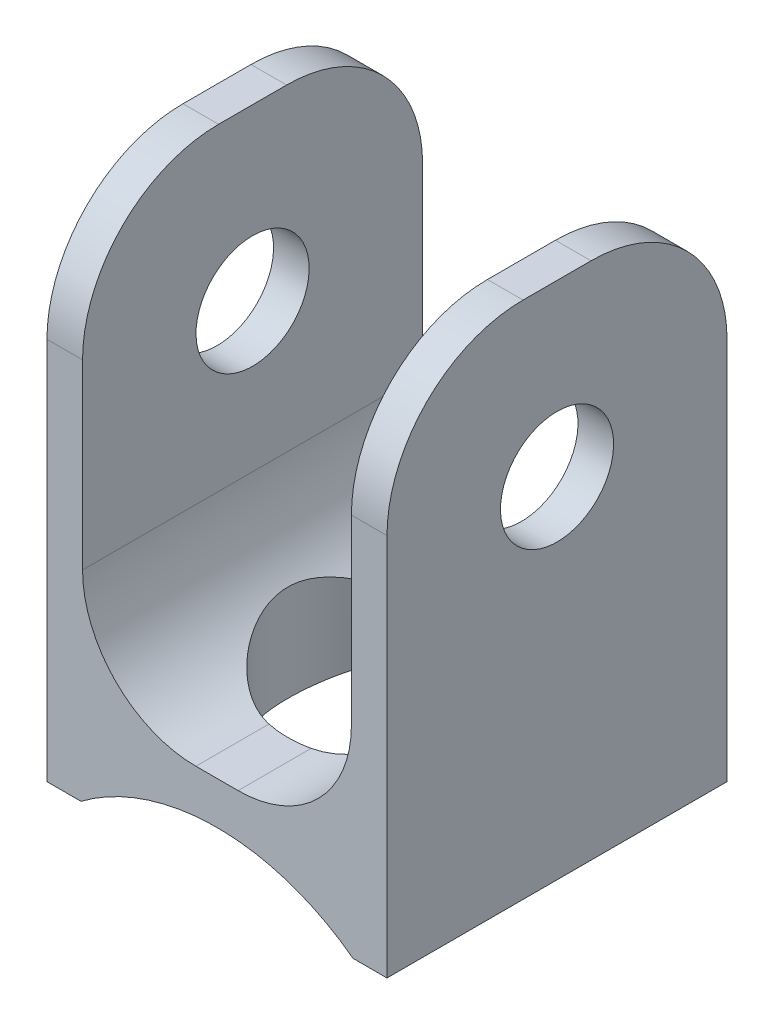
SolidWorks part; units mm, degrees
material "AISI 4130 Steel, annealed at 865C"
ref_plane "Plane1" through (0, 0, 0) normal (0, 0, 1) x (1, 0, 0)
ref_plane "Plane2" through (0, 0, 0) normal (0, 1, 0) x (1, 0, 0)
ref_plane "Plane3" through (0, 0, 0) normal (1, 0, 0) x (0, 0, -1)
ref_axis "Axis1" through (-83.9706, 0, 0) along (1, 0, 0)
ref_axis "Axis2" through (0, 0, -28.5687) along (0, 0, 1)
ref_axis "Axis3" through (0, 41.8402, 0) along (0, -1, 0)
sketch "Sketch1" plane through (0, 0, 0) normal (0, 0, 1) x (1, 0, 0)
  line L0 (0, 15.0812) -> (0, 0) construction
  line L1 (7.5311, 39.243) -> (9.525, 39.243)
  line L2 (-7.5311, 39.243) -> (-7.5311, 21.4312)
  line L3 (-1.1811, 15.0813) -> (1.1811, 15.0813)
  line L4 (7.5311, 39.243) -> (7.5311, 21.4312)
  line L5 (0, 39.243) -> (0, 15.0812) construction
  line L6 (-3.2512, 39.243) -> (-3.2512, 16.9862) construction
  line L7 (-3.2512, 16.9862) -> (3.2512, 16.9862) construction
  line L8 (3.2512, 16.9862) -> (3.2512, 39.243) construction
  line L9 (0, 29.718) -> (7.5311, 29.718) construction
  line L10 (9.525, 39.243) -> (9.525, 10.16)
  line L11 (9.525, 10.16) -> (7.62, 10.16)
  line L12 (7.5311, 39.243) -> (-7.5311, 39.243) construction
  line L13 (-7.5311, 39.243) -> (-9.525, 39.243)
  line L14 (-9.525, 39.243) -> (-9.525, 10.16)
  line L15 (-9.525, 10.16) -> (-7.62, 10.16)
  circle A0 centre (0, 0) radius 12.7 construction
  arc A1 (7.62, 10.16) -> (-7.62, 10.16) centre (0, 0) ccw
  arc A2 (1.1811, 15.0813) -> (7.5311, 21.4312) centre (1.1811, 21.4312) ccw
  arc A3 (-7.5311, 21.4312) -> (-1.1811, 15.0813) centre (-1.1811, 21.4312) ccw
  point P12 (0, 16.9862)
  dimension "D1" = 25.4
  dimension "D7" = 19.05
  dimension "D10" = 6.35
  dimension "D2" = 2.3813
  dimension "D3" = 15.0622
  dimension "D4" = 3.2512
  dimension "D5" = 1.905
  dimension "D6" = 29.718
  dimension "D8" = 1.905
  dimension "D9" = 9.525
extrude "Boss-Extrude1" add sketch "Sketch1" along normal mid plane 19.05
sketch "Sketch2" plane through (9.525, 0, 0) normal (1, 0, 0) x (0, 0, -1)
  line L0 (0, 29.718) -> (0, 0) construction
  line L1 (-9.525, 39.243) -> (9.525, 39.243) construction
  line L2 (-9.525, 10.16) -> (-9.525, 39.243) construction
  line L3 (-9.525, 31.623) -> (-9.525, 39.243)
  line L4 (-9.525, 39.243) -> (-1.905, 39.243)
  line L5 (9.525, 31.623) -> (9.525, 39.243)
  line L6 (9.525, 39.243) -> (1.905, 39.243)
  circle A0 centre (0, 29.718) radius 3.1686
  arc A1 (-9.525, 31.623) -> (-1.905, 39.243) centre (-1.905, 31.623) cw
  arc A2 (9.525, 31.623) -> (1.905, 39.243) centre (1.905, 31.623) ccw
  dimension "D1" = 9.525
  dimension "D2" = 6.3373
  dimension "D3" = 7.62
extrude "Cut-Extrude1" cut sketch "Sketch2" against normal through all
sketch "BEARING MATE POINT" plane through (0, 0, 0) normal (1, 0, 0) x (0, 0, -1)
  point P0 (0, 29.718)
sketch "Sketch3" plane through (0, 0, 0) normal (0, 1, 0) x (1, 0, 0)
  circle A0 centre (0, 0) radius 5.5562
  dimension "D1" = 11.1125
extrude "Cut-Extrude2" cut sketch "Sketch3" against normal through all both and the other way through all
